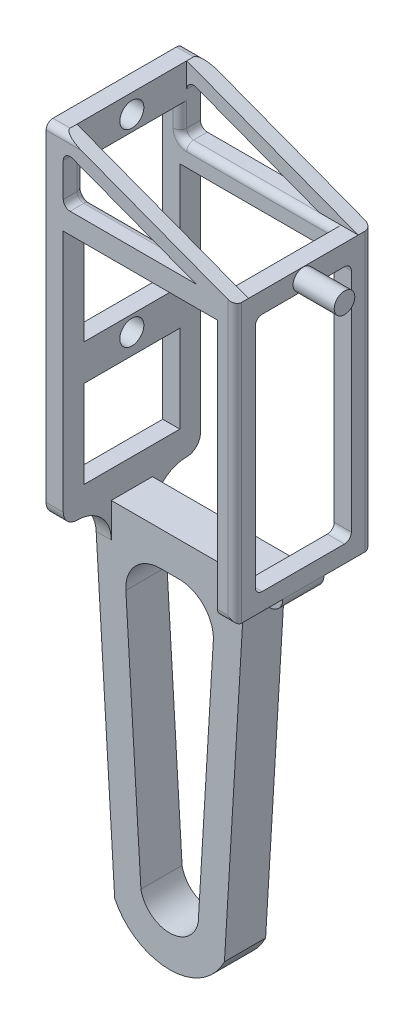
SolidWorks part; units mm, degrees
ref_plane "前视基准面" through (0, 0, 0) normal (0, 0, 1) x (1, 0, 0)
ref_plane "上视基准面" through (0, 0, 0) normal (0, 1, 0) x (1, 0, 0)
ref_plane "右视基准面" through (0, 0, 0) normal (1, 0, 0) x (0, 0, -1)
sketch "草图1" plane through (0, 0, 0) normal (0, 0, 1) x (1, 0, 0)
  line L0 (0, 0) -> (0, -100) construction
  line L1 (-11, -45) -> (11, -45)
  line L2 (-8, -95) -> (8, -95) construction
  line L3 (-8, -95) -> (-11, -45)
  line L4 (8, -95) -> (11, -45)
  arc A0 (-8, -95) -> (8, -95) centre (0, -91.1) ccw
  point P3 (0, -45)
  point P4 (0, -95)
  point P7 (0, -45)
  point P11 (0, -95)
  dimension "D1" = 100
  dimension "D2" = 55
  dimension "D3" = 22
  dimension "D4" = 5
  dimension "D5" = 16
extrude "凸台-拉伸1" add sketch "草图1" along normal mid plane 6
sketch "草图2" plane through (0, -45, 0) normal (0, 1, 0) x (1, 0, 0)
  line L0 (-12.1, 0) -> (12.1, 0) construction
  line L1 (-8.5, 10) -> (-11, 10)
  line L2 (-8.5, 10) -> (-8.5, -10)
  line L3 (-8.5, -10) -> (-11, -10)
  line L4 (-11, 10) -> (-11, -10)
  line L5 (-8.5, 10) -> (-11, -10) construction
  line L6 (-8.5, -10) -> (-11, 10) construction
  line L7 (-11, -3) -> (-11, 3) construction
  point P4 (-9.75, 0)
  dimension "D1" = 20
  dimension "D2" = 2.5
  dimension "D3" = 0
extrude "凸台-拉伸2" add sketch "草图2" along normal blind 22
sketch "草图3" plane through (0, -23, 0) normal (0, 1, 0) x (1, 0, 0)
  line L0 (-8.5, -10) -> (-8.5, 10) construction
  line L1 (-8.5, 10) -> (-11, 10)
  line L2 (-8.5, 10) -> (-8.5, 7)
  line L3 (-8.5, 7) -> (-11, 7)
  line L4 (-11, 10) -> (-11, 7)
  line L5 (-8.5, 10) -> (-11, 7) construction
  line L6 (-8.5, 7) -> (-11, 10) construction
  line L7 (-11, 10) -> (-11, -10) construction
  line L8 (-8.5, 10) -> (-11, 10) construction
  line L9 (-8.5, -10) -> (-11, -10)
  line L10 (-8.5, -10) -> (-8.5, -7)
  line L11 (-8.5, -7) -> (-11, -7)
  line L12 (-11, -10) -> (-11, -7)
  line L13 (-8.5, -10) -> (-11, -7) construction
  line L14 (-8.5, -7) -> (-11, -10) construction
  point P4 (-9.75, 8.5)
  point P14 (-9.75, -8.5)
  dimension "D1" = 3
  dimension "D2" = 3
extrude "凸台-拉伸3" add sketch "草图3" along normal blind 28
sketch "草图4" plane through (0, 0, -7) normal (0, 0, 1) x (1, 0, 0)
  line L0 (-8.5, 5) -> (-8.5, -23) construction
  line L1 (-11, 5) -> (-8.5, 5)
  line L2 (-11, 5) -> (-11, 0)
  line L3 (-11, 0) -> (-8.5, 0)
  line L4 (-8.5, 5) -> (-8.5, 0)
  line L5 (-11, 5) -> (-8.5, 0) construction
  line L6 (-11, 0) -> (-8.5, 5) construction
  point P4 (-9.75, 2.5)
  dimension "D1" = 5
extrude "凸台-拉伸4" add sketch "草图4" along normal up to next
sketch "草图5" plane through (-11, 0, 0) normal (-1, 0, 0) x (0, 0, 1)
  line L0 (0, -12.1) -> (0, 12.1) construction
  line L2 (-7, -23) -> (7, -23) construction
  circle A0 centre (0, -25.25) radius 1.75
  circle A1 centre (0, 2.25) radius 1.75
  dimension "D1" = 3.5
  dimension "D2" = 3.5
  dimension "D3" = 27.5
  dimension "D4" = 2.25
extrude "切除-拉伸1" cut sketch "草图5" against normal up to next
sketch "草图13" plane through (-8.5, 0, 0) normal (1, 0, 0) x (0, 0, -1)
  line L0 (-10, 5) -> (-10, -45) construction
  line L1 (-10, -4.5) -> (-7, -4.5)
  line L2 (-10, -4.5) -> (-10, -7.5)
  line L3 (-10, -7.5) -> (-7, -7.5)
  line L4 (-7, -4.5) -> (-7, -7.5)
  line L5 (-10, -4.5) -> (-7, -7.5) construction
  line L6 (-10, -7.5) -> (-7, -4.5) construction
  line L7 (-7, 0) -> (-7, -23) construction
  line L8 (7, 0) -> (7, -23) construction
  line L9 (7, -4.5) -> (10, -4.5)
  line L10 (7, -4.5) -> (7, -7.5)
  line L11 (7, -7.5) -> (10, -7.5)
  line L12 (10, -4.5) -> (10, -7.5)
  line L13 (7, -4.5) -> (10, -7.5) construction
  line L14 (7, -7.5) -> (10, -4.5) construction
  line L15 (10, 5) -> (10, -45) construction
  line L16 (-10, 5) -> (10, 5) construction
  point P4 (-8.5, -6)
  point P14 (8.5, -6)
  dimension "D1" = 11
  dimension "D2" = 3
  dimension "D3" = 3
extrude "凸台-拉伸9" add sketch "草图13" along normal blind 25
sketch "草图14" plane through (0, 0, -7) normal (0, 0, 1) x (1, 0, 0)
  line L0 (16.5, -4.5) -> (-8.5, -4.5) construction
  line L1 (16.5, -4.5) -> (14, -4.5)
  line L2 (16.5, -4.5) -> (16.5, -7.5)
  line L3 (16.5, -7.5) -> (14, -7.5)
  line L4 (14, -4.5) -> (14, -7.5)
  line L5 (16.5, -4.5) -> (14, -7.5) construction
  line L6 (16.5, -7.5) -> (14, -4.5) construction
  line L7 (16.5, -4.5) -> (16.5, -7.5) construction
  line L8 (16.5, -7.5) -> (-8.5, -7.5) construction
  point P4 (15.25, -6)
  dimension "D1" = 2.5
extrude "凸台-拉伸10" add sketch "草图14" along normal up to surface (14 mm away) up to face at (-2.875, -8.75, 7)
sketch "草图11" plane through (16.5, 0, 0) normal (1, 0, 0) x (0, 0, -1)
  circle A0 centre (0, -6.05) radius 1.5
  circle A1 centre (0, -6.05) radius 2 construction
  dimension "D1" = 3
extrude "凸台-拉伸8" add sketch "草图11" along normal blind 6
fillet "圆角1" radius 2 2 edges at (-9.75, -45, -10) (-9.75, -45, 10)
sketch "草图15" plane through (0, 0, 3) normal (0, 0, 1) x (1, 0, 0)
  line L0 (-6.6928, -50) -> (6.6928, -50)
  line L1 (6.6928, -50) -> (4.1773, -91.9246)
  line L3 (-4.1773, -91.9246) -> (-6.6928, -50)
  line L4 (-11, -45) -> (-8, -95) construction
  line L5 (8, -95) -> (11, -45) construction
  line L6 (11, -45) -> (-8.5, -45) construction
  line L7 (8, -95) -> (11, -45) construction
  arc A2 (-4.1773, -91.9246) -> (4.1773, -91.9246) centre (0, -91.1) ccw
  arc A3 (-8, -95) -> (8, -95) centre (0, -91.1) ccw construction
  dimension "D1" = 5
  dimension "D3" = 4
  dimension "D4" = 4
extrude "切除-拉伸2" cut sketch "草图15" against normal up to next
fillet "圆角5" radius 5 4 edges at (-6.6928, -50, 0) (6.6928, -50, 0) (-9.75, -45, -3) (-9.75, -45, 3)
ref_plane "基准面1" through (0, 0, 10) normal (0, 0, 1) x (1, 0, 0)
sketch "草图16" plane through (0, 0, 10) normal (0, 0, 1) x (1, 0, 0)
  line L0 (-8.5, 5) -> (16.5, -4.5)
  line L1 (16.5, -4.5) -> (10.8697, -4.5)
  line L2 (10.8697, -4.5) -> (-8.5, 2.8605)
  line L3 (-8.5, 5) -> (-8.5, -4.5) construction
  line L4 (-8.5, 2.8605) -> (-8.5, 5)
  dimension "D1" = 2
extrude "凸台-拉伸11" add sketch "草图16" against normal blind 2
mirror "镜向1" about plane through (0, 0, 0) normal (0, 0, 1) of "凸台-拉伸11"
sketch "草图17" plane through (0, -7.5, 0) normal (0, -1, 0) x (1, 0, 0)
  line L0 (16.5, -1.5) -> (16.5, 1.5) construction
  line L1 (16.5, 7) -> (14, 7)
  line L2 (16.5, 7) -> (16.5, 10)
  line L3 (16.5, 10) -> (14, 10)
  line L4 (14, 7) -> (14, 10)
  line L5 (16.5, 7) -> (14, 10) construction
  line L6 (16.5, 10) -> (14, 7) construction
  line L7 (16.5, -0.3841) -> (16.5, -10) construction
  line L8 (14, 7) -> (14, -7) construction
  line L11 (16.5, 10) -> (-8.5, 10) construction
  line L12 (14, 7) -> (-8.5, 7) construction
  line L13 (16.5, -10) -> (-8.5, -10) construction
  line L14 (14, -7) -> (16.5, -7)
  line L15 (14, -7) -> (14, -10)
  line L16 (14, -10) -> (16.5, -10)
  line L17 (16.5, -7) -> (16.5, -10)
  line L18 (14, -7) -> (16.5, -10) construction
  line L19 (14, -10) -> (16.5, -7) construction
  point P4 (15.25, 8.5)
  point P19 (15.25, -8.5)
extrude "凸台-拉伸12" add sketch "草图17" along normal up to surface (37.5 mm away) up to face at (1.25, -45, 0)
sketch "草图18" plane through (0, 0, -7) normal (0, 0, 1) x (1, 0, 0)
  line L0 (16.5, -45) -> (16.5, -7.5) construction
  line L1 (14, -45) -> (16.5, -45)
  line L2 (14, -45) -> (14, -42.5)
  line L3 (14, -42.5) -> (16.5, -42.5)
  line L4 (16.5, -45) -> (16.5, -42.5)
  line L5 (14, -45) -> (16.5, -42.5) construction
  line L6 (14, -42.5) -> (16.5, -45) construction
  point P4 (15.25, -43.75)
  dimension "D1" = 2.5
extrude "凸台-拉伸13" add sketch "草图18" along normal up to next
sketch "草图19" plane through (59, -45, 0) normal (0, 1, 0) x (0, 0, 1)
  line L1 (-3, -42.5) -> (3, -42.5)
  line L2 (-3, -42.5) -> (-3, -45)
  line L3 (-3, -45) -> (3, -45)
  line L4 (3, -42.5) -> (3, -45)
  line L5 (-3, -42.5) -> (3, -45) construction
  line L6 (-3, -45) -> (3, -42.5) construction
  line L8 (3, -48) -> (3, -67.5) construction
  line L9 (-3, -48) -> (-3, -67.5) construction
  line L10 (10, -45) -> (-10, -45) construction
  line L11 (-10, -42.5) -> (10, -42.5) construction
  point P4 (0, -43.75)
fillet "圆角8" radius 1 18 edges at (-8.5, 2.8605, -9) (-8.5, -4.5, -8.5) (-8.5, -4.5, 8.5) (-8.5, 2.8605, 9) (16.5, -24.75, -10) (16.5, -24.75, 10) (2.75, -4.5, 7) (2.75, -4.5, -7) (-8.5, -2.25, 7) (-8.5, -2.25, -7) (15.25, -42.5, 7) (15.25, -42.5, -7) (15.25, -45, -10) (15.25, -45, 10) (15.25, -7.5, -7) (15.25, -7.5, 7) (-9.75, 5, 10) (-9.75, 5, -10)
sketch "草图20" plane through (-11, 0, 0) normal (-1, 0, 0) x (0, 0, 1)
  line L0 (-7, 0) -> (-7, -23) construction
  line L1 (-7, -28.25) -> (7, -28.25)
  line L2 (-7, -28.25) -> (-7, -41)
  line L3 (-7, -41) -> (7, -41)
  line L4 (7, -28.25) -> (7, -41)
  line L5 (-7, -28.25) -> (7, -41) construction
  line L6 (-7, -41) -> (7, -28.25) construction
  line L7 (7, 0) -> (7, -23) construction
  line L8 (8, -45) -> (-8, -45) construction
  circle A0 centre (0, -25.25) radius 1.75 construction
  point P4 (0, -34.625)
  dimension "D1" = 4
  dimension "D2" = 3
extrude "切除-拉伸3" cut sketch "草图20" against normal up to next
extrude "凸台-拉伸15" add sketch "草图19" against normal blind 2
sketch "草图25" plane through (14, 0, 0) normal (-1, 0, 0) x (0, 0, 1)
  line L1 (-3, -45) -> (3, -45)
  line L2 (-3, -45) -> (-3, -47)
  line L3 (-3, -47) -> (3, -47)
  line L4 (3, -45) -> (3, -47)
  line L5 (-3, -45) -> (3, -47) construction
  line L6 (-3, -47) -> (3, -45) construction
  point P4 (0, -46)
extrude "凸台-拉伸16" add sketch "草图25" along normal up to next
fillet "圆角10" radius 2 3 edges at (16.5, -47, 0) (14, -45, 0) (10.88, -47, 0)
ref_plane "基准面2" through (0, -100, 0) normal (0, -1, 0) x (-1, 0, 0)
